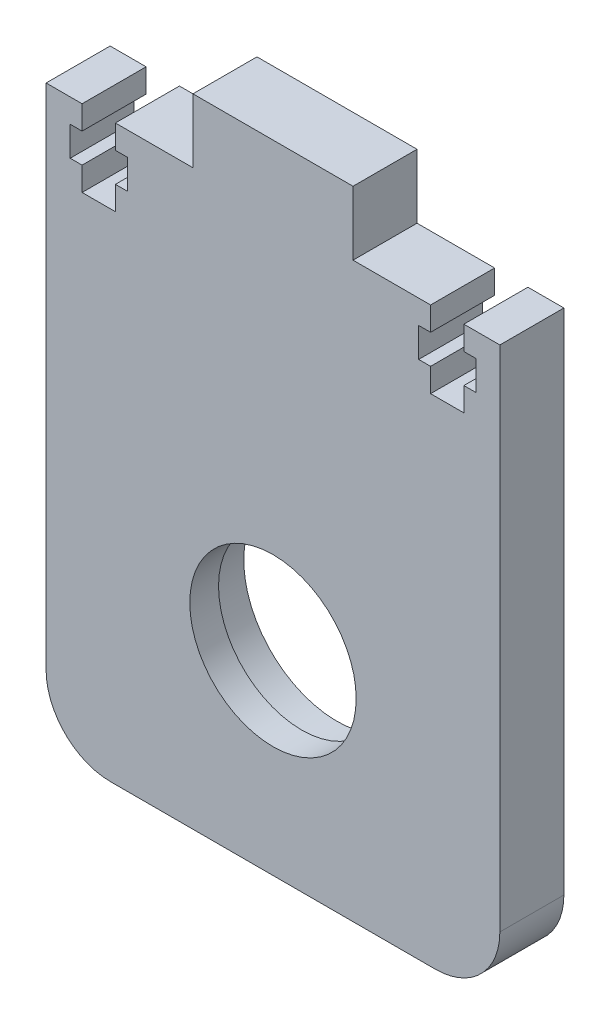
SolidWorks part; units mm, degrees
ref_plane "Front Plane" through (0, 0, 0) normal (0, 0, 1) x (1, 0, 0)
ref_plane "Top Plane" through (0, 0, 0) normal (0, 1, 0) x (1, 0, 0)
ref_plane "Right Plane" through (0, 0, 0) normal (1, 0, 0) x (0, 0, -1)
sketch "Sketch12" plane through (0, 0, 0) normal (0, 0, 1) x (1, 0, 0)
  line L0 (62.1258, 0) -> (62.1258, 113.63)
  line L1 (62.1258, 113.63) -> (152.1258, 113.63)
  line L2 (62.1258, 0) -> (152.1258, 0)
  line L3 (152.1258, 113.63) -> (152.1258, 0)
  circle A0 centre (99.6258, 37.5) radius 25.4
  circle A1 centre (99.6258, 37.5) radius 6.5
  dimension "D3" = 50.8
  dimension "D4" = 13
  dimension "D1" = 113.63
  dimension "D2" = 90
extrude "Boss-Extrude10" add sketch "Sketch12" along normal blind 12.7 separate body contours L1 L3 L2 L0
sketch "Sketch15" plane through (0, 0, 12.7) normal (0, 0, 1) x (1, 0, 0)
  line L0 (62.1258, 0) -> (152.1258, 0) construction
  circle A0 centre (107.1258, 38.6276) radius 25.4
  point P2 (0, 0)
  point P7 (107.1258, 0)
  dimension "D1" = 50.8
  dimension "D2" = 38.6276
sketch "Sketch24" plane through (0, 0, 12.7) normal (0, 0, 1) x (1, 0, 0)
  line L0 (62.1258, 113.63) -> (62.1258, 109.63)
  line L1 (62.1258, 0) -> (62.1258, 113.63) construction
  line L2 (62.1258, 109.63) -> (152.1258, 109.63)
  line L3 (152.1258, 113.63) -> (152.1258, 0) construction
  line L4 (152.1258, 109.63) -> (152.1258, 113.63)
  line L5 (152.1258, 113.63) -> (62.1258, 113.63)
  dimension "D1" = 4
sketch "Sketch25" plane through (0, 0, 12.7) normal (0, 0, 1) x (1, 0, 0)
  circle A0 centre (107.1258, 38.6276) radius 18.5
  dimension "D1" = 37
extrude "Cut-Extrude1" cut sketch "Sketch25" against normal through all
sketch "Sketch26" plane through (0, 0, 12.7) normal (0, 0, 1) x (1, 0, 0)
  circle A0 centre (107.1258, 38.6276) radius 16.5
  circle A1 centre (107.1258, 38.6276) radius 18.5
  dimension "D1" = 37
  dimension "D2" = 2
extrude "Boss-Extrude15" add sketch "Sketch26" against normal blind 5.7
fillet "Fillet1" radius 12.8 2 edges at (152.1258, 0, 6.35) (62.1258, 0, 6.35)
sketch "Sketch27" plane through (0, 0, 0) normal (0, 0, -1) x (-1, 0, 0)
  line L0 (-69.2638, 113.63) -> (-69.2638, 108.931)
  line L1 (-152.1258, 113.63) -> (-62.1258, 113.63) construction
  line L2 (-69.2638, 108.931) -> (-66.9018, 108.931)
  line L3 (-66.9018, 108.931) -> (-66.9018, 103.089)
  line L4 (-66.9018, 103.089) -> (-69.2638, 103.089)
  line L5 (-69.2638, 103.089) -> (-69.2638, 98.39)
  line L6 (-69.2638, 98.39) -> (-75.8678, 98.39)
  line L7 (-75.8678, 98.39) -> (-75.8678, 103.089)
  line L8 (-75.8678, 103.089) -> (-78.2298, 103.089)
  line L9 (-78.2298, 103.089) -> (-78.2298, 108.931)
  line L10 (-78.2298, 108.931) -> (-75.8678, 108.931)
  line L11 (-75.8678, 108.931) -> (-75.8678, 113.63)
  line L12 (-75.8678, 113.63) -> (-69.2638, 113.63)
  line L13 (-138.3838, 108.931) -> (-138.3838, 113.63)
  line L15 (-107.1258, 113.63) -> (-107.1258, 67.3255)
  line L28 (-136.0218, 108.931) -> (-138.3838, 108.931)
  line L29 (-136.0218, 103.089) -> (-136.0218, 108.931)
  line L30 (-138.3838, 103.089) -> (-136.0218, 103.089)
  line L31 (-138.3838, 98.39) -> (-138.3838, 103.089)
  line L32 (-144.9878, 98.39) -> (-138.3838, 98.39)
  line L33 (-144.9878, 103.089) -> (-144.9878, 98.39)
  line L34 (-147.3498, 103.089) -> (-144.9878, 103.089)
  line L35 (-147.3498, 108.931) -> (-147.3498, 103.089)
  line L36 (-144.9878, 108.931) -> (-147.3498, 108.931)
  line L37 (-144.9878, 113.63) -> (-144.9878, 108.931)
  line L38 (-138.3838, 113.63) -> (-144.9878, 113.63)
  line L39 (-72.5658, 113.63) -> (-107.1258, 113.63)
  line L40 (-107.1258, 113.63) -> (-141.6858, 113.63)
  point P22 (-72.5658, 113.63)
  point P29 (-141.6858, 113.63)
  point P31 (0, 0)
  line M19 (-62.1258, 113.63) -> (-152.1258, 113.63)
  dimension "D1" = 6.604
  dimension "D2" = 11.328
  dimension "D3" = 5.842
  dimension "D4" = 15.24
  dimension "D5" = 69.12
ref_axis "Axis2" through (107.1258, 113.63, 0) along (0, -1, 0)
extrude "Cut-Extrude2" cut sketch "Sketch27" against normal through all contours L11 L10 L9 L8 L7 L6 L5 L4 L3 L2 L0 M19 | L37 L36 L35 L34 L33 L32 L31 L30 L29 L28 L13 M19 region at (141.6858, 106.01, 0) region at (72.5658, 106.01, 0)
sketch "Sketch28" plane through (0, 113.63, 0) normal (0, 1, 0) x (1, 0, 0)
  line L0 (107.1258, 0) -> (91.2508, 0)
  line L1 (75.8678, 0) -> (138.3838, 0) construction
  line L2 (91.2508, 0) -> (91.2508, -12.7)
  line L3 (81.7258, -12.7) -> (132.5258, -12.7) construction
  line L4 (91.2508, -12.7) -> (123.0008, -12.7)
  line L5 (123.0008, -12.7) -> (123.0008, 0)
  line L6 (123.0008, 0) -> (107.1258, 0)
  dimension "D1" = 31.75
extrude "Boss-Extrude16" add sketch "Sketch28" along normal blind 12.7
